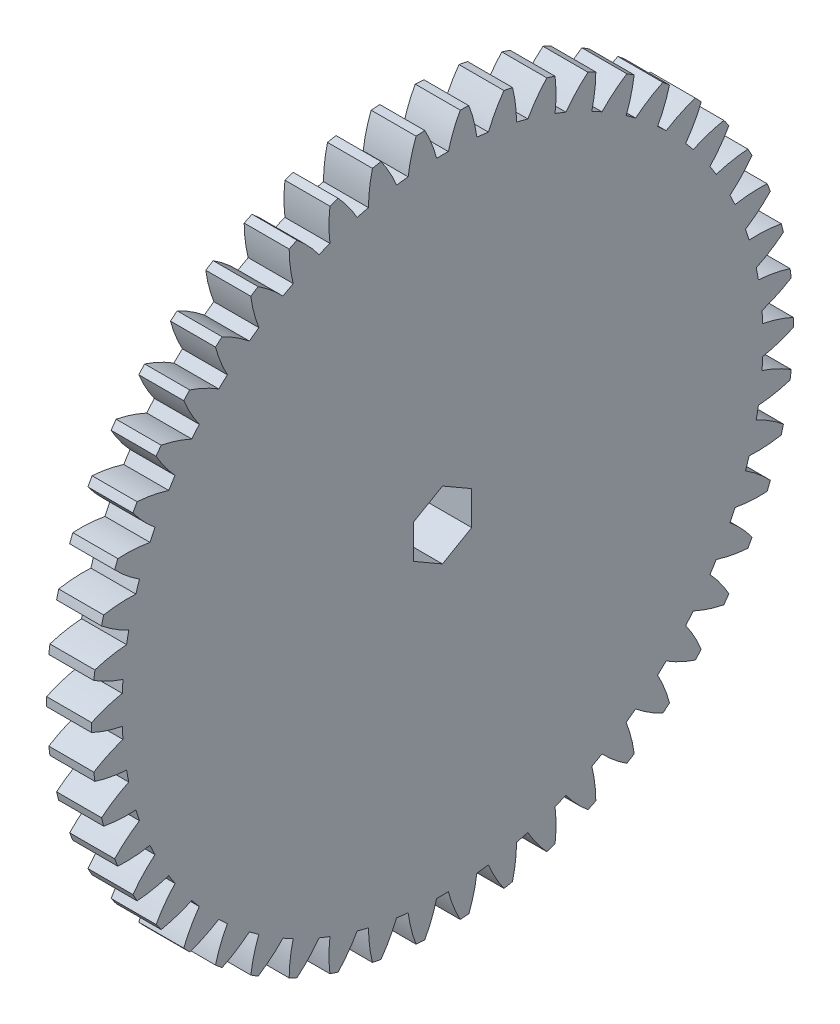
SolidWorks part; units mm, degrees
ref_plane "Plane1" through (0, 0, 0) normal (0, 0, 1) x (1, 0, 0)
ref_plane "Plane2" through (0, 0, 0) normal (0, 1, 0) x (1, 0, 0)
ref_plane "Plane3" through (0, 0, 0) normal (1, 0, 0) x (0, 0, -1)
sketch "HoldingSke" plane through (0, 0, 0) normal (0, 1, 0) x (1, 0, 0)
  line L0 (0, 0) -> (0.4285, -0.5107)
  line L1 (-15, 0) -> (100, 0) construction
  line L2 (0, 0) -> (-2.1039, 2.3779)
  line L3 (0, 0) -> (-11.863, 4.5341)
  line L4 (0, 0) -> (5.5511, 6.6156)
  line L5 (0, 0) -> (-46.8476, -17.4728)
  line L6 (0, 0) -> (-4.1448, -2.7965)
  line L7 (-2.1039, 2.3779) -> (8.6586, 51.2059)
  line L8 (-76.2, 54.61) -> (-75.3, 54.61)
  line L9 (-71.009, 38.7566) -> (-53.1078, 45.2721)
  line L10 (-76.2, 71.12) -> (104.1128, 71.12)
  line L11 (0, 0) -> (-5, 0)
  line L12 (-76.2, 101.6) -> (-76.147, 101.6)
  line L13 (24.9733, 27.94) -> (52.9518, 28.4284)
  line L14 (24.9733, 27.94) -> (24.9743, 27.94)
  line L15 (24.9733, 27.94) -> (100.4006, 29.5858)
  line L16 (-63.627, -1.5) -> (-12.827, -1.5)
  circle A0 centre (0, 0) radius 2.5
  circle A1 centre (0, 0) radius 35.624
  circle A2 centre (0, 0) radius 37.5
  circle A3 centre (0, 0) radius 2.5
  dimension "MHD" = 71.248
  dimension "Hub_dia" = 75
  dimension "Bore" = 5
  dimension "MBD" = 5
  dimension "Num_teeth" = 50
  dimension "Pitch" = 0.6667
  dimension "Overall_len" = 50
  dimension "Show_teeth" = 50
  dimension "Thickness" = 5
  dimension "OAL" = 50.0001
  dimension "T_dim" = 0.9
  dimension "Ap" = 20
  dimension "H" = 19.05
  dimension "Pitch_radius" = 180.3128
  dimension "Width" = 5
  dimension "Backlash" = 0.053
  dimension "Addendum_fac" = 1
  dimension "Dedendum_fac" = 1.25
  dimension "Clearance_fac" = 0.25
  dimension "Dedendum_add" = 0.001
  dimension "Module" = 1.5
sketch "BasProSke" plane through (0, 0, 0) normal (0, 1, 0) x (1, 0, 0)
  line L0 (-10, 0) -> (60, 0) construction
  line L1 (0, 0) -> (0, 39)
  line L2 (0, 0) -> (5, 0)
  line L3 (5, 0) -> (5, 39)
  line L4 (5, 39) -> (0, 39)
  dimension "Thickness" = 5
  dimension "Diameter" = 78
revolve "Base-Revolve" add sketch "BasProSke" angle 360 about L0
sketch "TooCutSke" plane through (0, 0, 0) normal (1, 0, 0) x (0, 0, -1)
  line L1 (0, 0) -> (0, 107) construction
  line L2 (0, 0) -> (-1.2706, 37.4785) construction
  line L3 (0, 0) -> (-4.7073, 74.8207) construction
  line L4 (-1.2706, 37.4785) -> (-2.3537, 37.4103) construction
  arc A0 (0.65, 35.6181) -> (-0.65, 35.6181) centre (0, 0) ccw
  arc A1 (1.9801, 38.9751) -> (-1.9801, 38.9751) centre (0, 0) ccw
  circle A2 centre (0, 0) radius 37.5 construction
  circle A3 centre (0, 0) radius 35.2385 construction
  arc A4 (-0.65, 35.6181) -> (-1.9801, 38.9751) centre (-15.1589, 31.8113) ccw
  arc A5 (1.9801, 38.9751) -> (0.65, 35.6181) centre (15.1589, 31.8113) ccw
  dimension "Root_dia" = 71.248
  dimension "Overcut_dia" = 78.0508
  dimension "Pitch_dia" = 75
  dimension "Base_dia" = 70.4769
  dimension "Flank_rad" = 15
  dimension "Half_ang" = 3.6
  dimension "Half_CT" = 1.0852
extrude "ToothCut" cut sketch "TooCutSke" along normal through all
fillet "Breaks" [suppressed] radius 0.03 tangent propagation no
fillet "RootFillets" [suppressed] radius 0.376
pattern_circular "TeethCuts" count 50 every 7.2 about axis through (-10, 0, 0) along (1, 0, 0) of "ToothCut", "RootFillets", "Breaks"
sketch "HubNeaOneSke" plane through (0, 0, 0) normal (-1, 0, 0) x (0, 0, 1)
  circle A0 centre (0, 0) radius 35.624
  dimension "Diameter" = 71.248
extrude "HubNearOne" [suppressed] add sketch "HubNeaOneSke" along normal blind 45.0001
sketch "HubNeaBotSke" plane through (0, 0, 0) normal (-1, 0, 0) x (0, 0, 1)
  circle A0 centre (0, 0) radius 35.624
  dimension "Diameter" = 71.248
extrude "HubNearBoth" [suppressed] add sketch "HubNeaBotSke" along normal blind 22.5
ref_plane "FarPln" through (5, 0, 0) normal (1, 0, 0) x (0, 0, -1)
sketch "HubFarSke" plane through (5, 0, 0) normal (1, 0, 0) x (0, 0, -1)
  circle A0 centre (0, 0) radius 35.624
  dimension "Diameter" = 71.248
extrude "HubFar" [suppressed] add sketch "HubFarSke" along normal blind 22.5
sketch "BorSke" plane through (0, 0, 0) normal (1, 0, 0) x (0, 0, -1)
  line L1 (0, -3.75) -> (3.2476, -1.875)
  line L2 (3.2476, -1.875) -> (3.2476, 1.875)
  line L3 (3.2476, 1.875) -> (0, 3.75)
  line L4 (0, 3.75) -> (-3.2476, 1.875)
  line L5 (-3.2476, 1.875) -> (-3.2476, -1.875)
  line L6 (-3.2476, -1.875) -> (0, -3.75)
  circle A0 centre (0, 0) radius 3.75 construction
  circle A1 centre (0, 0) radius 3.2476 construction
  dimension "Diameter" = 7.5
extrude "Bore" cut sketch "BorSke" along normal mid plane 100.0001
sketch "KeySke" plane through (0, 0, 0) normal (1, 0, 0) x (0, 0, -1)
  line L0 (-1, 0) -> (-1, 3.4)
  line L1 (-1, 3.4) -> (1, 3.4)
  line L2 (1, 3.4) -> (1, 0)
  line L3 (0, 0) -> (0, 34) construction
  line L4 (-1, 0) -> (1, 0)
  dimension "Offset" = 3.4
  dimension "Width" = 2
extrude "Keyway" [suppressed] cut sketch "KeySke" along normal mid plane 100.0001
pattern_circular "Keyway2" [suppressed] count 2 every 90 about axis through (-10, 0, 0) along (1, 0, 0) reverse direction yes
sketch "Sketch1" plane through (0, 0, 0) normal (-1, 0, 0) x (0, 0, 1)
  line L12 (3.2476, -1.875) -> (3.2476, 1.875) construction
  line L13 (3.2476, 1.875) -> (0, 3.75) construction
  line L14 (0, 3.75) -> (-3.2476, 1.875) construction
  line L15 (-3.2476, 1.875) -> (-3.2476, -1.875) construction
  line L16 (-3.2476, -1.875) -> (0, -3.75) construction
  line L17 (0, -3.75) -> (3.2476, -1.875) construction
  line L18 (3.2476, -1.875) -> (3.2476, 1.875)
  line L19 (3.2476, 1.875) -> (0, 3.75)
  line L20 (0, 3.75) -> (-3.2476, 1.875)
  line L21 (-3.2476, 1.875) -> (-3.2476, -1.875)
  line L22 (-3.2476, -1.875) -> (0, -3.75)
  line L23 (0, -3.75) -> (3.2476, -1.875)
  line L24 (4.5499, -3.3057) -> (-4.5499, 3.3057) construction
  arc A40 (0.1868, -8.9981) -> (0.8757, -5.5554) centre (-1.8542, -6.7994) ccw
  arc A41 (-0.1868, -8.9981) -> (0.1868, -8.9981) centre (0, 0) ccw
  arc A42 (-0.8757, -5.5554) -> (-0.1868, -8.9981) centre (1.8542, -6.7994) ccw
  arc A43 (-2.5569, -5.0091) -> (-0.8757, -5.5554) centre (0, 0) ccw
  arc A44 (-5.1378, -7.3894) -> (-2.5569, -5.0091) centre (-5.4967, -4.4109) ccw
  arc A45 (-5.4401, -7.1698) -> (-5.1378, -7.3894) centre (0, 0) ccw
  arc A46 (-3.9738, -3.9797) -> (-5.4401, -7.1698) centre (-2.4965, -6.5907) ccw
  arc A47 (-5.0129, -2.5496) -> (-3.9738, -3.9797) centre (0, 0) ccw
  arc A48 (-8.4999, -2.9582) -> (-5.0129, -2.5496) centre (-7.0396, -0.3377) ccw
  arc A49 (-8.6154, -2.6029) -> (-8.4999, -2.9582) centre (0, 0) ccw
  arc A50 (-5.5541, -0.8839) -> (-8.6154, -2.6029) centre (-5.8936, -3.8646) ccw
  arc A51 (-5.5541, 0.8839) -> (-5.5541, -0.8839) centre (0, 0) ccw
  arc A52 (-8.6154, 2.6029) -> (-5.5541, 0.8839) centre (-5.8936, 3.8646) ccw
  arc A53 (-8.4999, 2.9582) -> (-8.6154, 2.6029) centre (0, 0) ccw
  arc A54 (-5.0129, 2.5496) -> (-8.4999, 2.9582) centre (-7.0396, 0.3377) ccw
  arc A55 (-3.9738, 3.9797) -> (-5.0129, 2.5496) centre (0, 0) ccw
  arc A56 (-5.4401, 7.1698) -> (-3.9738, 3.9797) centre (-2.4965, 6.5907) ccw
  arc A57 (-5.1378, 7.3894) -> (-5.4401, 7.1698) centre (0, 0) ccw
  arc A58 (-2.5569, 5.0091) -> (-5.1378, 7.3894) centre (-5.4967, 4.4109) ccw
  arc A59 (-0.8757, 5.5554) -> (-2.5569, 5.0091) centre (0, 0) ccw
  arc A60 (-0.1868, 8.9981) -> (-0.8757, 5.5554) centre (1.8542, 6.7994) ccw
  arc A61 (0.1868, 8.9981) -> (-0.1868, 8.9981) centre (0, 0) ccw
  arc A62 (0.8757, 5.5554) -> (0.1868, 8.9981) centre (-1.8542, 6.7994) ccw
  arc A63 (2.5569, 5.0091) -> (0.8757, 5.5554) centre (0, 0) ccw
  arc A64 (5.1378, 7.3894) -> (2.5569, 5.0091) centre (5.4967, 4.4109) ccw
  arc A65 (5.4401, 7.1698) -> (5.1378, 7.3894) centre (0, 0) ccw
  arc A66 (3.9738, 3.9797) -> (5.4401, 7.1698) centre (2.4965, 6.5907) ccw
  arc A67 (5.0129, 2.5496) -> (3.9738, 3.9797) centre (0, 0) ccw
  arc A68 (8.4999, 2.9582) -> (5.0129, 2.5496) centre (7.0396, 0.3377) ccw
  arc A69 (8.6154, 2.6029) -> (8.4999, 2.9582) centre (0, 0) ccw
  arc A70 (5.5541, 0.8839) -> (8.6154, 2.6029) centre (5.8936, 3.8646) ccw
  arc A71 (5.5541, -0.8839) -> (5.5541, 0.8839) centre (0, 0) ccw
  arc A72 (8.6154, -2.6029) -> (5.5541, -0.8839) centre (5.8936, -3.8646) ccw
  arc A73 (8.4999, -2.9582) -> (8.6154, -2.6029) centre (0, 0) ccw
  arc A74 (5.0129, -2.5496) -> (8.4999, -2.9582) centre (7.0396, -0.3377) ccw
  arc A75 (3.9738, -3.9797) -> (5.0129, -2.5496) centre (0, 0) ccw
  arc A76 (5.4401, -7.1698) -> (3.9738, -3.9797) centre (2.4965, -6.5907) ccw
  arc A77 (5.1378, -7.3894) -> (5.4401, -7.1698) centre (0, 0) ccw
  arc A78 (2.5569, -5.0091) -> (5.1378, -7.3894) centre (5.4967, -4.4109) ccw
  arc A79 (0.8757, -5.5554) -> (2.5569, -5.0091) centre (0, 0) ccw
extrude "Boss-Extrude1" add sketch "Sketch1" along normal blind 10
equation "' \"Module@HoldingSke\" = 6.35"
equation "' \"Num_teeth@HoldingSke\" = 12"
equation "' \"Ap@HoldingSke\" =  20"
equation "' \"Ap@HoldingSke\" = 20"
equation "' \"Width@HoldingSke\" = 0.5 * 25.4"
equation "' \"Hub_dia@HoldingSke\"= 1 * 25.4"
equation "' \"Hub_dia@HoldingSke\" = 1 * 25.4"
equation "' \"Overall_len@HoldingSke\" = 1.0 * 25.4"
equation "' \"Bore@HoldingSke\" = 0.75 * 25.4"
equation "' \"T_dim@HoldingSke\" = 0.1 * 25.4"
equation "' \"Width@KeySke\" = 0.25 * 25.4"
equation "' \"Show_teeth@HoldingSke\" = 13"
equation "' \"Backlash@HoldingSke\" = 0.009 * 25.4"
equation "' \"Addendum_fac@HoldingSke\" = 1.0"
equation "' \"Dedendum_fac@HoldingSke\" = 1.25"
equation "' \"Dedendum_add@HoldingSke\" = 0.00005 * 25.4"
equation "' \"Clearance_fac@HoldingSke\" = 0.25"
equation "\"Pitch@HoldingSke\" = 1 / \"Module@HoldingSke\""
equation "\"Overcut_dia@TooCutSke\" = (\"Num_teeth@HoldingSke\" + 2 * \"Addendum_fac@HoldingSke\") / \"Pitch@HoldingSke\" + 0.002 * 25.4"
equation "\"Pitch_dia@TooCutSke\" = \"Num_teeth@HoldingSke\" / \"Pitch@HoldingSke\""
equation "\"Base_dia@TooCutSke\" = \"Num_teeth@HoldingSke\" / \"Pitch@HoldingSke\" * cos((\"Ap@HoldingSke\"  * 3.14159265 / 180))"
equation "\"Root_dia@TooCutSke\" = (\"Num_teeth@HoldingSke\" + 2) / \"Pitch@HoldingSke\" - 2 * (\"Addendum_fac@HoldingSke\" + \"Dedendum_fac@HoldingSke\") / \"Pitch@HoldingSke\" - \"Dedendum_add@HoldingSke\" * 2"
equation "\"Half_ang@TooCutSke\" = 180 / \"Num_teeth@HoldingSke\""
equation "\"Half_CT@TooCutSke\" = \"Num_teeth@HoldingSke\" / \"Pitch@HoldingSke\" * sin((3.14159265 / 2 / \"Num_teeth@HoldingSke\")) / 2 - 7 * \"Backlash@HoldingSke\" / 4"
equation "\"Flank_rad@TooCutSke\" = \"Num_teeth@HoldingSke\" / \"Pitch@HoldingSke\" / 5"
equation "\"Radius@RootFillets\" = \"Clearance_fac@HoldingSke\" / \"Pitch@HoldingSke\" + \"Dedendum_add@HoldingSke\""
equation "\"Break_rad@Breaks\" = 0.02 / \"Pitch@HoldingSke\""
equation "\"Thickness@HoldingSke\" = \"Width@HoldingSke\""
equation "\"OAL@HoldingSke\" = \"Thickness@HoldingSke\""
equation "\"MHD@HoldingSke\" = (\"Num_teeth@HoldingSke\" + 2) / \"Pitch@HoldingSke\" - 2 * (\"Addendum_fac@HoldingSke\" + \"Dedendum_fac@HoldingSke\")  / \"Pitch@HoldingSke\" - \"Dedendum_add@HoldingSke\" * 2"
equation "\"MBD@HoldingSke\" = (\"Num_teeth@HoldingSke\" + 2) / \"Pitch@HoldingSke\" - 2 * (\"Addendum_fac@HoldingSke\" + \"Dedendum_fac@HoldingSke\")  / \"Pitch@HoldingSke\" - \"Dedendum_add@HoldingSke\" * 2 - 0.002 * 25.4"
equation "\"MHD@HoldingSke\" = ((sgn( \"MHD@HoldingSke\" - \"Hub_dia@HoldingSke\" )-1)*( \"MHD@HoldingSke\" - \"Hub_dia@HoldingSke\" ))/-2+ \"Hub_dia@HoldingSke\""
equation "\"MBD@HoldingSke\" = ((sgn( \"MBD@HoldingSke\" - \"Bore@HoldingSke\" )-1)*( \"MBD@HoldingSke\" - \"Bore@HoldingSke\" ))/-2+ \"Bore@HoldingSke\""
equation "\"OAL@HoldingSke\" = ((sgn( \"OAL@HoldingSke\" - \"Overall_len@HoldingSke\" )+1)*( \"OAL@HoldingSke\" - \"Overall_len@HoldingSke\" ))/2 + \"Overall_len@HoldingSke\" + 0.000002 * 25.4"
equation "\"Num_teeth@TeethCuts\" = int( \"Show_teeth@HoldingSke\" ) + 1"
equation "\"Num_teeth@TeethCuts\" = ((sgn( \"Num_teeth@TeethCuts\" - \"Num_teeth@HoldingSke\" )-1)*( \"Num_teeth@TeethCuts\" - \"Num_teeth@HoldingSke\" ))/-2+ \"Num_teeth@HoldingSke\""
equation "\"Num_teeth@TeethCuts\" = ((sgn( \"Num_teeth@TeethCuts\" - 2.0)+1)*( \"Num_teeth@TeethCuts\" - 2.0))/2 +2.0"
equation "\"Angle@TeethCuts\" = 360.0 / \"Num_teeth@HoldingSke\""
equation "\"Diameter@BasProSke\" = (\"Num_teeth@HoldingSke\" + 2 * \"Addendum_fac@HoldingSke\") / \"Pitch@HoldingSke\""
equation "\"Thickness@BasProSke\"  = \"Thickness@HoldingSke\""
equation "' \"Fillet_rad@BasProSke\" =  \"Thickness@HoldingSke\" * 0.05"
equation "' \"Fillet_rad@BasProSke\" = \"Thickness@HoldingSke\" * 0.05"
equation "\"MHD@HoldingSke\" = ((sgn( \"MHD@HoldingSke\" - \"Root_dia@TooCutSke\" )-1)*( \"MHD@HoldingSke\" - \"Root_dia@TooCutSke\" ))/-2+ \"Root_dia@TooCutSke\""
equation "\"Diameter@HubNeaOneSke\" = \"MHD@HoldingSke\""
equation "\"Length@HubNearOne\" = \"OAL@HoldingSke\" - \"Thickness@BasProSke\""
equation "\"Diameter@HubNeaBotSke\" = \"MHD@HoldingSke\""
equation "\"Length@HubNearBoth\" = ( \"OAL@HoldingSke\" - \"Thickness@BasProSke\" ) / 2.0"
equation "\"Thickness@FarPln\" = \"Thickness@BasProSke\""
equation "\"Diameter@HubFarSke\" = \"MHD@HoldingSke\""
equation "\"Length@HubFar\" = ( \"OAL@HoldingSke\" - \"Thickness@BasProSke\" ) / 2.0"
equation "\"Diameter@BorSke\"=7.5"
equation "\"D1@Bore\" = \"OAL@HoldingSke\" * 2.0"
equation "\"D1@Keyway\" = \"OAL@HoldingSke\" * 2.0"
equation "\"Offset@KeySke\" = \"T_dim@HoldingSke\" + \"MBD@HoldingSke\" / 2.0"
